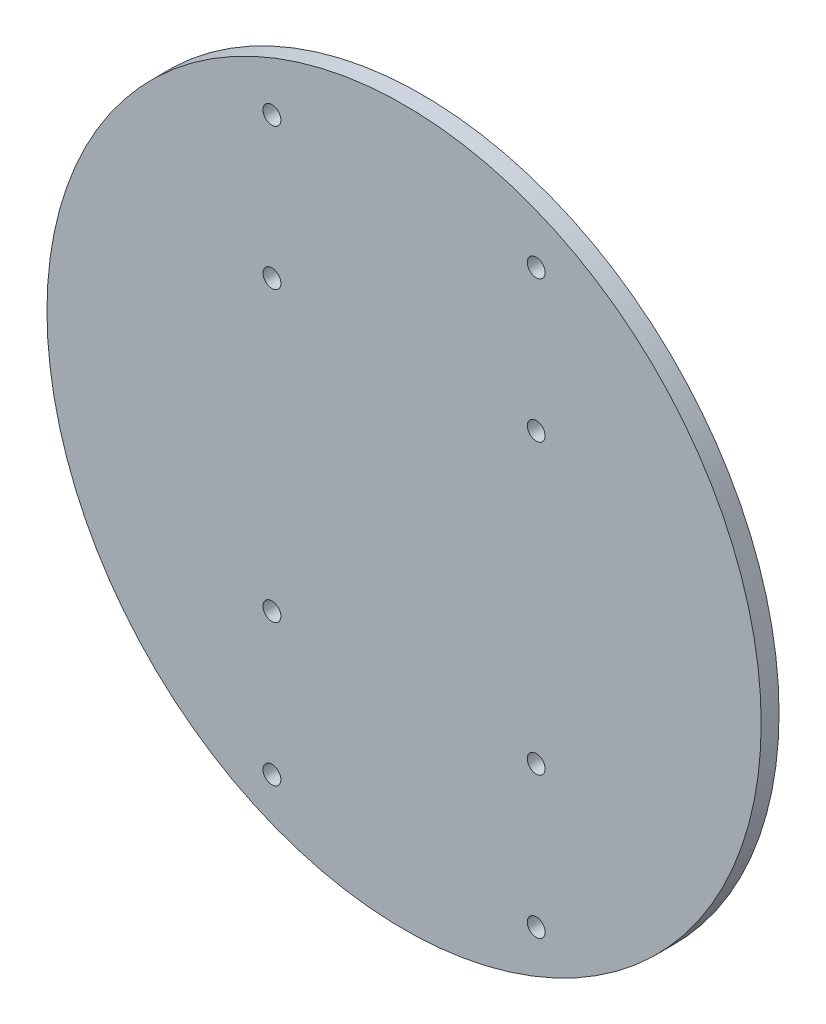
SolidWorks part; units mm, degrees
ref_plane "Alzado" through (0, 0, 0) normal (0, 0, 1) x (1, 0, 0)
ref_plane "Planta" through (0, 0, 0) normal (0, 1, 0) x (1, 0, 0)
ref_plane "Vista lateral" through (0, 0, 0) normal (1, 0, 0) x (0, 0, -1)
sketch "Croquis1" plane through (0, 0, 0) normal (0, 0, 1) x (1, 0, 0)
  circle A0 centre (0, 0) radius 82.42
  dimension "D1" = 164.84
extrude "Saliente-Extruir1" add sketch "Croquis1" along normal blind 5
sketch "Croquis2" plane through (0, 0, 5) normal (0, 0, 1) x (1, 0, 0)
  circle A0 centre (0, 0) radius 100
  dimension "D1" = 200
extrude "Saliente-Extruir2" add sketch "Croquis2" against normal up to surface (5 mm away) up to face at (82.42, 0, 0)
sketch "Croquis3" plane through (0, 0, 5) normal (0, 0, 1) x (1, 0, 0)
  line L0 (0, 0) -> (0, 100) construction
  line L1 (-37, -80.9032) -> (-37, -41.3032) construction
  line L2 (0, 0) -> (-100, 0) construction
  line L3 (0, 0) -> (100, 0) construction
  line L4 (0, -80.9032) -> (-37, -80.9032) construction
  line L5 (0, -80.9032) -> (37, -80.9032) construction
  line L6 (-37, -80.9032) -> (-37, -92.9032) construction
  line L7 (-37, -41.3032) -> (37, -41.3032) construction
  line L8 (0, 0) -> (0, -100) construction
  line L9 (37, -41.3032) -> (37, -80.9032) construction
  line L10 (-37, -41.3032) -> (-37, -35.3032) construction
  line L11 (-37, -35.3032) -> (-37, 33.4468) construction
  line L12 (-37, 33.4468) -> (-37, 39.4468) construction
  line L13 (-37, 39.4468) -> (37, 39.4468) construction
  line L14 (37, 39.4468) -> (37, -35.3032) construction
  line L15 (37, -35.3032) -> (37, -41.3032) construction
  line L16 (-37, 39.4468) -> (-37, 79.0468) construction
  line L17 (37, 39.4468) -> (37, 79.0468) construction
  line L18 (-37, 79.0468) -> (37, 79.0468) construction
  circle A0 centre (0, 0) radius 100 construction
  circle A1 centre (-37, -80.9032) radius 2.5
  circle A2 centre (37, -80.9032) radius 2.5
  circle A4 centre (-37, -41.3032) radius 2.5
  circle A5 centre (37, -41.3032) radius 2.5
  circle A6 centre (-37, 39.4468) radius 2.5
  circle A7 centre (37, 39.4468) radius 2.5
  circle A8 centre (-37, 79.0468) radius 2.5
  circle A9 centre (37, 79.0468) radius 2.5
  dimension "D2" = 5
  dimension "D3" = 5
  dimension "D8" = 5
  dimension "D9" = 6
  dimension "D7" = 5
  dimension "D12" = 5
  dimension "D14" = 5
  dimension "D17" = 5
  dimension "D18" = 5
  dimension "D1" = 12
  dimension "D4" = 37
  dimension "D5" = 37
  dimension "D6" = 39.6
  dimension "D10" = 68.75
  dimension "D11" = 6
  dimension "D13" = 74
  dimension "D15" = 39.6
  dimension "D16" = 39.6
extrude "Cortar-Extruir1" cut sketch "Croquis3" against normal blind 10
